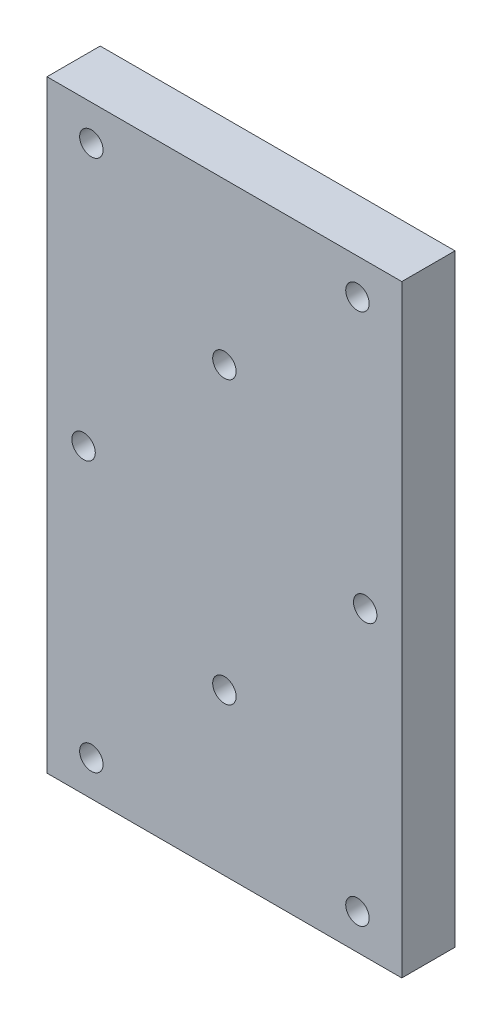
SolidWorks part; units mm, degrees
ref_plane "Front Plane" through (0, 0, 0) normal (0, 0, 1) x (1, 0, 0)
ref_plane "Top Plane" through (0, 0, 0) normal (0, 1, 0) x (1, 0, 0)
ref_plane "Right Plane" through (0, 0, 0) normal (1, 0, 0) x (0, 0, -1)
sketch "Sketch1" plane through (0, 0, 0) normal (0, 0, 1) x (1, 0, 0)
  line L0 (-20, 34) -> (20, -34) construction
  line L1 (20, 34) -> (-20, 34)
  line L2 (20, 34) -> (20, -34)
  line L3 (20, -34) -> (-20, -34)
  line L4 (-20, 34) -> (-20, -34)
  line L5 (20, 34) -> (-20, -34) construction
  line L6 (0, 0) -> (0, -26.0057) construction
  line L7 (0.5075, 0) -> (50000.5075, 0) construction
  line L8 (0, 0) -> (0, -50000) construction
  line L9 (-15, 30) -> (15, -30) construction
  line L10 (0, 0) -> (5.2736, 3.5775) construction
  line L13 (-15, -30) -> (15, -30) construction
  line L14 (15, -30) -> (15, 30) construction
  line L15 (15, 30) -> (-15, 30) construction
  line L16 (-15, 30) -> (-15, -30) construction
  circle A0 centre (0, -15.875) radius 1.32
  circle A1 centre (-15.875, 0) radius 1.32
  circle A2 centre (0, 15.875) radius 1.32
  circle A3 centre (15.875, 0) radius 1.32
  circle A4 centre (-15, 30) radius 1.32
  circle A5 centre (15, 30) radius 1.32
  circle A6 centre (15, -30) radius 1.32
  circle A7 centre (-15, -30) radius 1.32
  point P29 (0, 0)
  dimension "D3" = 2.64
  dimension "D10" = 2.64
  dimension "D13" = 30
  dimension "D14" = 60
  dimension "D1" = 40
  dimension "D2" = 68
  dimension "D4" = 15.875
  dimension "D11" = 2
  dimension "D12" = 2
  dimension "D5" = 4
extrude "Boss-Extrude1" add sketch "Sketch1" along normal blind 6
sketch "Sketch2" plane through (0, 0, 0) normal (0, 0, -1) x (-1, 0, 0)
  circle A0 centre (0, 15.875) radius 3.25
  circle A1 centre (0, 15.875) radius 1.32 construction
  circle A2 centre (15.875, 0) radius 3.25
  circle A3 centre (0, -15.875) radius 3.25
  circle A4 centre (-15.875, 0) radius 3.25
  point P14 (0, 0)
  dimension "D1" = 6.5
  dimension "D2" = 4
extrude "Cut-Extrude1" cut sketch "Sketch2" against normal blind 4
